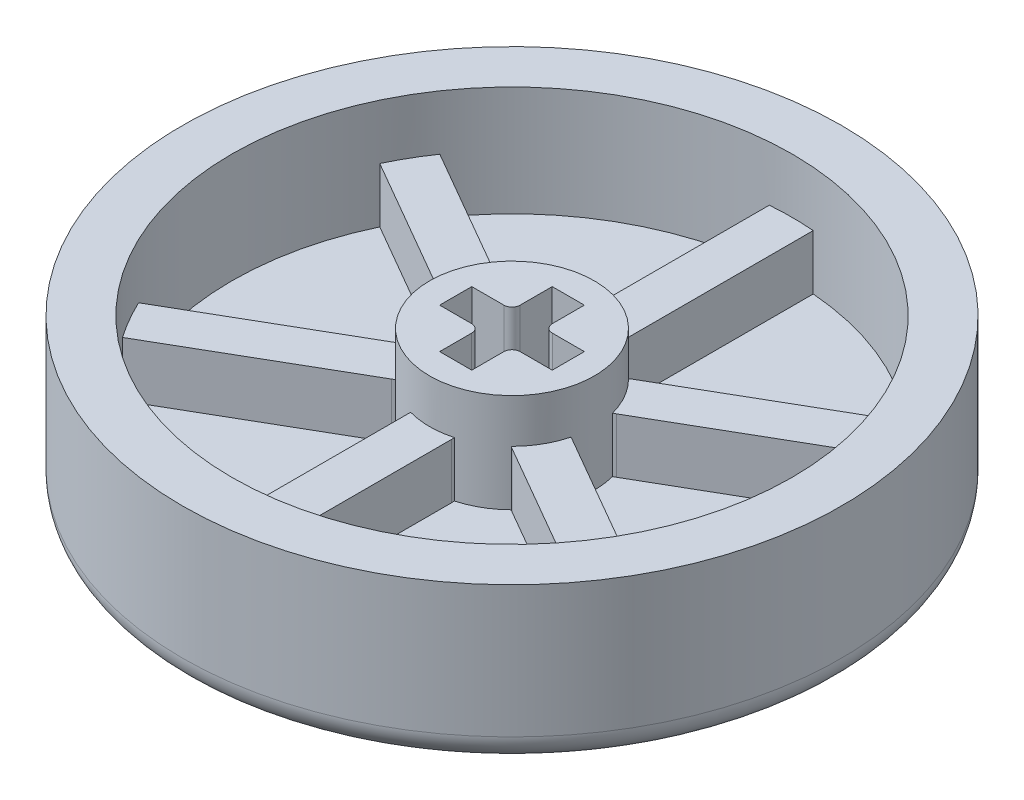
SolidWorks part; units mm, degrees
ref_plane "Front Plane" through (0, 0, 0) normal (0, 0, 1) x (1, 0, 0)
ref_plane "Top Plane" through (0, 0, 0) normal (0, 1, 0) x (1, 0, 0)
ref_plane "Right Plane" through (0, 0, 0) normal (1, 0, 0) x (0, 0, -1)
sketch "Sketch1" plane through (0, 0, 0) normal (0, 1, 0) x (1, 0, 0)
  circle A0 centre (0, 0) radius 12
  dimension "D1" = 24
extrude "button top" add sketch "Sketch1" along normal blind 1.8
sketch "Sketch2" plane through (0, 1.8, 0) normal (0, 1, 0) x (1, 0, 0)
  circle A3 centre (0, 0) radius 12
  circle A4 centre (0, 0) radius 12 construction
  circle A5 centre (0, 0) radius 10.2
  dimension "D1" = 1.8
extrude "button walls" add sketch "Sketch2" along normal blind 4
sketch "Sketch3" plane through (0, 1.8, 0) normal (0, 1, 0) x (1, 0, 0)
  line L0 (0, -2.05) -> (0, 2.05) construction
  line L1 (-2.05, 0) -> (2.05, 0) construction
  line L2 (-0.585, 0.885) -> (-0.585, 2.05)
  line L3 (-0.585, -2.05) -> (0.585, -2.05)
  line L4 (-0.585, -2.05) -> (-0.585, -0.885)
  line L5 (-0.585, 2.05) -> (0.585, 2.05)
  line L6 (0.585, -2.05) -> (0.585, -0.885)
  line L7 (-0.585, -2.05) -> (0.585, 2.05) construction
  line L8 (-0.585, 2.05) -> (0.585, -2.05) construction
  line L9 (-2.05, -0.585) -> (-0.885, -0.585)
  line L10 (-2.05, -0.585) -> (-2.05, 0.585)
  line L11 (-2.05, 0.585) -> (-0.885, 0.585)
  line L12 (2.05, -0.585) -> (2.05, 0.585)
  line L13 (-2.05, -0.585) -> (2.05, 0.585) construction
  line L14 (-2.05, 0.585) -> (2.05, -0.585) construction
  line L15 (0.885, 0.585) -> (2.05, 0.585)
  line L16 (0.585, 0.885) -> (0.585, 2.05)
  line L17 (0.885, -0.585) -> (2.05, -0.585)
  circle A0 centre (0, 0) radius 3
  arc A1 (-0.585, -0.885) -> (-0.885, -0.585) centre (-0.885, -0.885) ccw
  arc A2 (0.585, -0.885) -> (0.885, -0.585) centre (0.885, -0.885) cw
  arc A3 (0.885, 0.585) -> (0.585, 0.885) centre (0.885, 0.885) cw
  arc A4 (-0.585, 0.885) -> (-0.885, 0.585) centre (-0.885, 0.885) cw
  point P6 (0, 0)
  point P9 (0, 0)
  point P22 (2.05, 0)
  point P24 (0, 2.05)
  point P29 (0.585, -0.585)
  point P32 (0.585, 0.585)
  dimension "D1" = 6
  dimension "D4" = 0.3
  dimension "D2" = 4.1
  dimension "D3" = 1.17
extrude "stem housing" add sketch "Sketch3" along normal blind 3.6
sketch "Sketch4" plane through (0, 1.8, 0) normal (0, 1, 0) x (1, 0, 0)
  line L0 (0, 3) -> (0, 10.2) construction
  line L1 (-0.8, 3) -> (-0.8, 10.2)
  line L2 (0.8, 3) -> (0.8, 10.2)
  line L3 (2.5981, 1.5) -> (8.8335, 5.1) construction
  line L4 (2.1981, 2.1928) -> (8.4335, 5.7928)
  line L5 (2.9981, 0.8072) -> (9.2335, 4.4072)
  line L6 (2.5981, -1.5) -> (8.8335, -5.1) construction
  line L7 (2.9981, -0.8072) -> (9.2335, -4.4072)
  line L8 (2.1981, -2.1928) -> (8.4335, -5.7928)
  line L9 (0, -3) -> (0, -10.2) construction
  line L10 (0.8, -3) -> (0.8, -10.2)
  line L11 (-0.8, -3) -> (-0.8, -10.2)
  line L12 (-2.5981, -1.5) -> (-8.8335, -5.1) construction
  line L13 (-2.1981, -2.1928) -> (-8.4335, -5.7928)
  line L14 (-2.9981, -0.8072) -> (-9.2335, -4.4072)
  line L15 (-2.5981, 1.5) -> (-8.8335, 5.1) construction
  line L16 (-2.9981, 0.8072) -> (-9.2335, 4.4072)
  line L17 (-2.1981, 2.1928) -> (-8.4335, 5.7928)
  circle A0 centre (0, 0) radius 3 construction
  circle A1 centre (0, 0) radius 3 construction
  circle A2 centre (0, 0) radius 10.2 construction
  arc A3 (-0.8, 3) -> (0.8, 3) centre (0, 3) ccw
  arc A4 (0.8, 10.2) -> (-0.8, 10.2) centre (0, 10.2) ccw
  arc A5 (2.1981, 2.1928) -> (2.9981, 0.8072) centre (2.5981, 1.5) ccw
  arc A6 (9.2335, 4.4072) -> (8.4335, 5.7928) centre (8.8335, 5.1) ccw
  arc A7 (2.9981, -0.8072) -> (2.1981, -2.1928) centre (2.5981, -1.5) ccw
  arc A8 (8.4335, -5.7928) -> (9.2335, -4.4072) centre (8.8335, -5.1) ccw
  arc A9 (0.8, -3) -> (-0.8, -3) centre (0, -3) ccw
  arc A10 (-0.8, -10.2) -> (0.8, -10.2) centre (0, -10.2) ccw
  arc A11 (-2.1981, -2.1928) -> (-2.9981, -0.8072) centre (-2.5981, -1.5) ccw
  arc A12 (-9.2335, -4.4072) -> (-8.4335, -5.7928) centre (-8.8335, -5.1) ccw
  arc A13 (-2.9981, 0.8072) -> (-2.1981, 2.1928) centre (-2.5981, 1.5) ccw
  arc A14 (-8.4335, 5.7928) -> (-9.2335, 4.4072) centre (-8.8335, 5.1) ccw
  point P9 (0, 6.6)
  point P18 (5.7158, 3.3)
  point P25 (5.7158, -3.3)
  point P32 (0, -6.6)
  point P39 (-5.7158, -3.3)
  point P46 (-5.7158, 3.3)
  point P51 (0, 0)
  dimension "D1" = 1.6
  dimension "D2" = 6
extrude "Boss-Extrude4" add sketch "Sketch4" along normal blind 2
fillet "Fillet1" radius 1 1 edges at (0, 0, 12)
